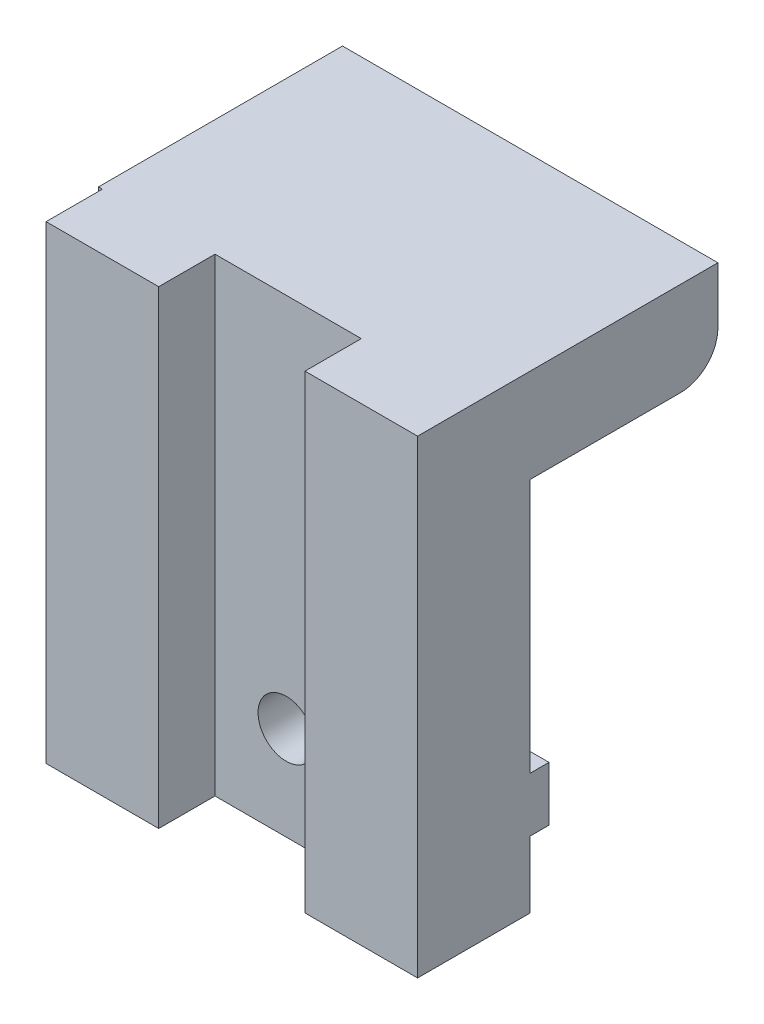
SolidWorks part; units mm, degrees
ref_plane "Front Plane" through (0, 0, 0) normal (0, 0, 1) x (1, 0, 0)
ref_plane "Top Plane" through (0, 0, 0) normal (0, 1, 0) x (1, 0, 0)
ref_plane "Right Plane" through (0, 0, 0) normal (1, 0, 0) x (0, 0, -1)
sketch "Esquisse1" plane through (0, 0, 0) normal (0, 0, 1) x (1, 0, 0)
  line L0 (-10, -12.5) -> (10, -12.5)
  line L1 (10, -12.5) -> (10, 12.5)
  line L2 (10, 12.5) -> (-10, 12.5)
  line L3 (-10, 12.5) -> (-10, -12.5)
  point P3 (0, 12.5)
  point P7 (-10, 0)
  dimension "D1" = 20
  dimension "D2" = 25
extrude "Boss.-Extru.1" add sketch "Esquisse1" along normal blind 3
sketch "Esquisse2" plane through (0, 0, 0) normal (0, 0, -1) x (-1, 0, 0)
  line L0 (10, 12.5) -> (10, -12.5) construction
  line L1 (-10, 12.5) -> (10, 12.5)
  line L2 (-10, 12.5) -> (-10, 7.5)
  line L3 (-10, 7.5) -> (10, 7.5)
  line L4 (10, 12.5) -> (10, 7.5)
  dimension "D1" = 5
extrude "Boss.-Extru.2" add sketch "Esquisse2" along normal blind 10
fillet "Congé2" radius 2 1 edges at (0, 7.5, -10)
sketch "Esquisse3" plane through (0, 0, 0) normal (0, 0, -1) x (-1, 0, 0)
  line L0 (-10, -12.5) -> (-10, 7.5) construction
  line L1 (-10, -8.95) -> (10, -8.95)
  line L2 (-10, -8.95) -> (-10, -6.05)
  line L3 (-10, -6.05) -> (10, -6.05)
  line L4 (10, -8.95) -> (10, -6.05)
  line L5 (10, 7.5) -> (10, -12.5) construction
  line L6 (10, -12.5) -> (-10, -12.5) construction
  point P8 (-10, -7.5)
  dimension "D1" = 5
  dimension "D2" = 2.9
extrude "Boss.-Extru.3" add sketch "Esquisse3" along normal blind 1
sketch "Esquisse4" plane through (0, 0, 3) normal (0, 0, 1) x (1, 0, 0)
  line L0 (-10, -12.5) -> (10, -12.5) construction
  circle A0 centre (0, -7.5) radius 1.5
  point P4 (0, 0)
  point P5 (0, -12.5)
  dimension "D1" = 3
  dimension "D2" = 5
extrude "Enlèv. mat.-Extru.1" cut sketch "Esquisse4" against normal through all
sketch "Esquisse5" plane through (0, 0, 3) normal (0, 0, 1) x (1, 0, 0)
  line L0 (10, 12.5) -> (-10, 12.5) construction
  line L1 (-9.7917, 12.5) -> (-3.7917, 12.5)
  line L2 (-9.7917, 12.5) -> (-9.7917, -12.5)
  line L3 (-9.7917, -12.5) -> (-3.7917, -12.5)
  line L4 (-3.7917, 12.5) -> (-3.7917, -12.5)
  line L5 (-10, -12.5) -> (10, -12.5) construction
  line L7 (4, 12.5) -> (10, 12.5)
  line L8 (4, 12.5) -> (4, -12.5)
  line L9 (4, -12.5) -> (10, -12.5)
  line L10 (10, 12.5) -> (10, -12.5)
  dimension "D1" = 6
extrude "Boss.-Extru.4" add sketch "Esquisse5" along normal blind 3
